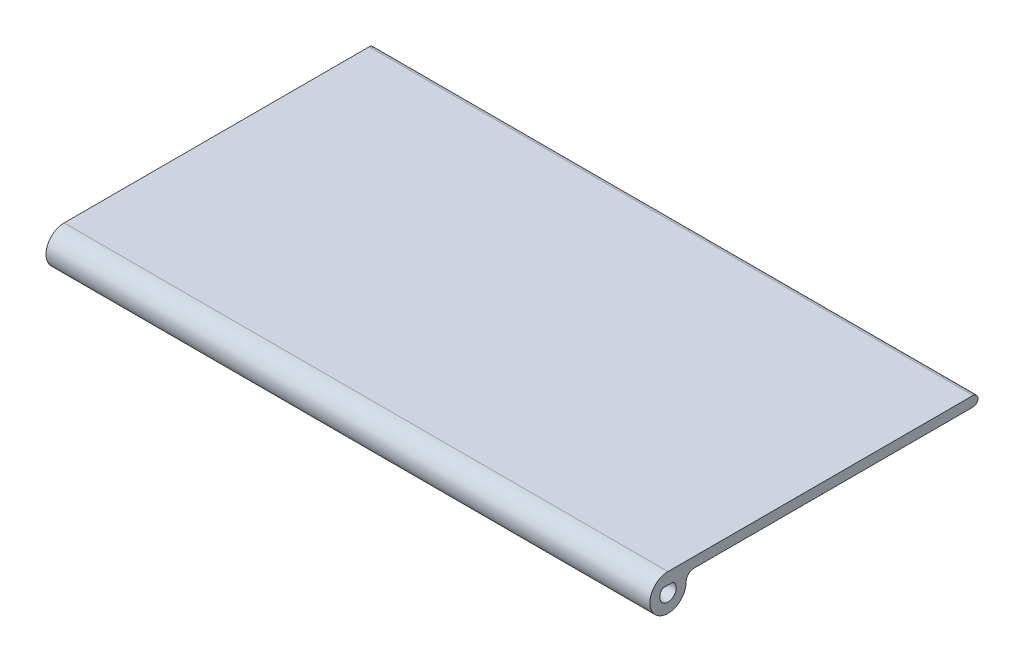
SolidWorks part; units mm, degrees
material "PLA - Approx"
ref_plane "Front Plane" through (0, 0, 0) normal (0, 0, 1) x (1, 0, 0)
ref_plane "Top Plane" through (0, 0, 0) normal (0, 1, 0) x (1, 0, 0)
ref_plane "Right Plane" through (0, 0, 0) normal (1, 0, 0) x (0, 0, -1)
other "Center of Mass"
sketch "Sketch1" plane through (0, 0, 0) normal (1, 0, 0) x (0, 0, -1)
  circle A0 centre (0, 0) radius 9
  dimension "D1" = 18
extrude "Boss-Extrude1" add sketch "Sketch1" along normal blind 300
sketch "Sketch2" plane through (300, 0, 0) normal (1, 0, 0) x (0, 0, -1)
  line L0 (-2.5632, 3.2) -> (2.5632, 3.2)
  arc A0 (-2.5632, 3.2) -> (2.5632, 3.2) centre (0, 0) ccw
  dimension "D2" = 8.2
  dimension "D1" = 3.2
extrude "Cut-Extrude1" cut sketch "Sketch2" against normal through all both and the other way through all
sketch "Sketch3" plane through (300, 0, 0) normal (1, 0, 0) x (0, 0, -1)
  line L0 (0, 0) -> (0, 9) construction
  line L1 (0, 9) -> (154, 9)
  line L2 (0, 9) -> (0, 4)
  line L3 (0, 4) -> (154, 4)
  line L4 (154, 9) -> (154, 4)
  line L5 (0, 0) -> (9, 0) construction
  arc A0 (9, 0) -> (13, 4) centre (13, 0) cw
  circle A1 centre (0, 0) radius 9 construction
  arc A2 (9, 0) -> (5, 4) centre (5, 0) ccw
  circle M7 centre (0, 0) radius 9
  dimension "D1" = 154
  dimension "D2" = 5
  dimension "D3" = 4
  dimension "D4" = 4
extrude "Boss-Extrude2" add sketch "Sketch3" against normal up to surface (300 mm away) contours A0 L3 M7 | A2 L3 M7 | L4 L1 L3 M7 | L2 L3 M7 region at (300, 6.0569, -3.1784) region at (300, 6.5172, -79.8726) region at (300, 3.0814, -9.5856) region at (300, 3.1595, -7.7663) up to face at (0, -0.45, 0)
sketch "Sketch4" plane through (300, 0, 0) normal (1, 0, 0) x (0, 0, -1)
  line L3 (151.5, 9) -> (154, 9)
  line L4 (154, 9) -> (154, 4)
  line L5 (154, 4) -> (151.5, 4)
  arc A1 (151.5, 4) -> (151.5, 9) centre (151.5, 6.5) ccw
extrude "Cut-Extrude2" cut sketch "Sketch4" against normal through all both and the other way through all
